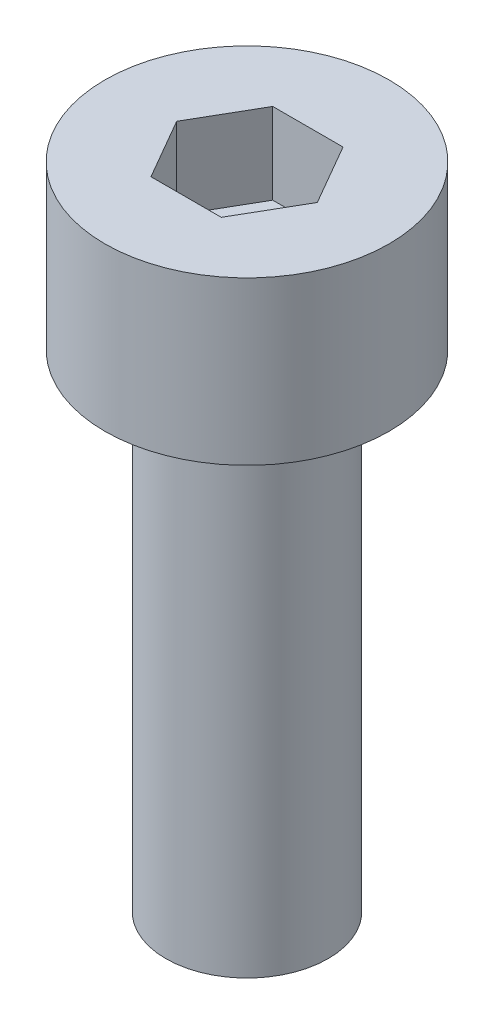
SolidWorks part; units mm, degrees
material "普通碳钢"
ref_plane "前视基准面" through (0, 0, 0) normal (0, 0, 1) x (1, 0, 0)
ref_plane "上视基准面" through (0, 0, 0) normal (0, 1, 0) x (1, 0, 0)
ref_plane "右视基准面" through (0, 0, 0) normal (1, 0, 0) x (0, 0, -1)
sketch "草图1" plane through (0, 0, 0) normal (0, 1, 0) x (1, 0, 0)
  circle A0 centre (0, 0) radius 2
  circle A1 centre (0, 0) radius 3.5
  dimension "公称直径" = 4
  dimension "外径" = 7
extrude "头部高" add sketch "草图1" along normal blind 4 contours A0 | A1 A0 region at (0, 0, 0) region at (-3.401, 0, 0)
extrude "公称长度" add sketch "草图1<3>" against normal blind 12 contours A0 region at (0, 0, 0)
sketch "草图1<3>" plane through (0, 0, 0) normal (0, 1, 0) x (1, 0, 0) same geometry as "草图1"
sketch "草图2" plane through (0, 4, 0) normal (0, 1, 0) x (1, 0, 0)
  line L1 (1.7321, 0) -> (0.866, 1.5)
  line L2 (0.866, 1.5) -> (-0.866, 1.5)
  line L3 (-0.866, 1.5) -> (-1.7321, 0)
  line L4 (-1.7321, 0) -> (-0.866, -1.5)
  line L5 (-0.866, -1.5) -> (0.866, -1.5)
  line L6 (0.866, -1.5) -> (1.7321, 0)
  circle A0 centre (0, 0) radius 1.5 construction
  dimension "D1" = 3
extrude "切除-拉伸1" cut sketch "草图2" against normal blind 2
